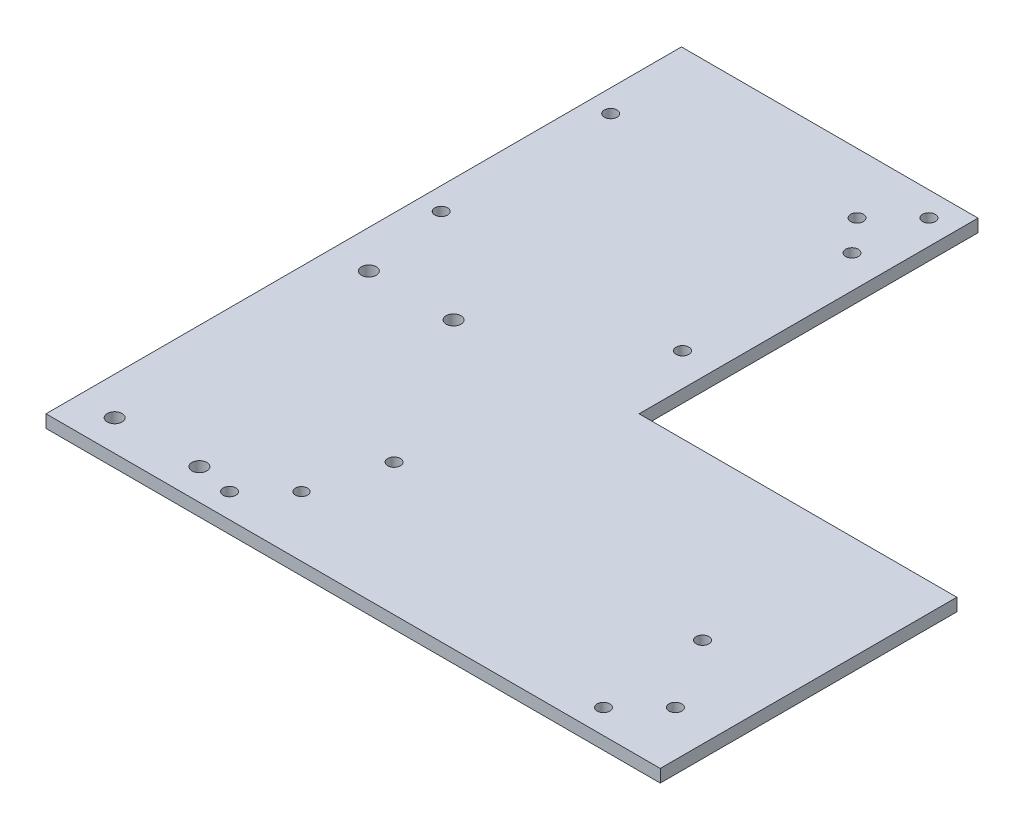
SolidWorks part; units mm, degrees
ref_plane "Front Plane" through (0, 0, 0) normal (0, 0, 1) x (1, 0, 0)
ref_plane "Top Plane" through (0, 0, 0) normal (0, 1, 0) x (1, 0, 0)
ref_plane "Right Plane" through (0, 0, 0) normal (1, 0, 0) x (0, 0, -1)
sketch "Sketch1" plane through (0, 0, 0) normal (0, 1, 0) x (1, 0, 0)
  line L0 (-72.5, -35) -> (72.5, -35)
  line L2 (-72.5, -35) -> (-72.5, 35)
  line L4 (72.5, -35) -> (72.5, 35)
  line L5 (-72.5, -35) -> (72.5, 35) construction
  line L6 (-72.5, 35) -> (72.5, -35) construction
  line L15 (-2.5, 35) -> (72.5, 35)
  line L17 (-72.5, 35) -> (-72.5, 115)
  line L18 (-72.5, 115) -> (-2.5, 115)
  line L19 (-2.5, 35) -> (-2.5, 115)
  circle A0 centre (-34.9264, -29.2426) radius 1.5
  circle A1 centre (-26.4411, -20.7574) radius 1.4446
  circle A2 centre (53.3381, -29.2426) radius 1.5
  circle A3 centre (61.8234, -20.7574) radius 1.5
  circle A4 centre (-16.8144, 100.7574) radius 1.5
  circle A5 centre (-8.3291, 109.2426) radius 1.5
  circle A6 centre (-21.5352, -3.8022) radius 1.5
  circle A7 centre (51.2739, -3.8022) radius 1.5
  circle A8 centre (-63.5846, -27.7106) radius 1.75
  circle A9 centre (-43.5846, -27.7106) radius 1.75
  circle A10 centre (-43.5846, 32.2894) radius 1.75
  circle A11 centre (-63.5846, 32.2894) radius 1.75
  circle A12 centre (-67.2195, 53.0097) radius 1.5
  circle A13 centre (-67.2195, 93.0097) radius 1.5
  circle A14 centre (-10.2613, 93.0097) radius 1.5
  circle A15 centre (-10.2613, 53.0097) radius 1.5
  point P0 (0, 0)
  dimension "D1" = 145
  dimension "D2" = 70
  dimension "D3" = 70
  dimension "D4" = 150
extrude "Boss-Extrude1" add sketch "Sketch1" along normal blind 3
